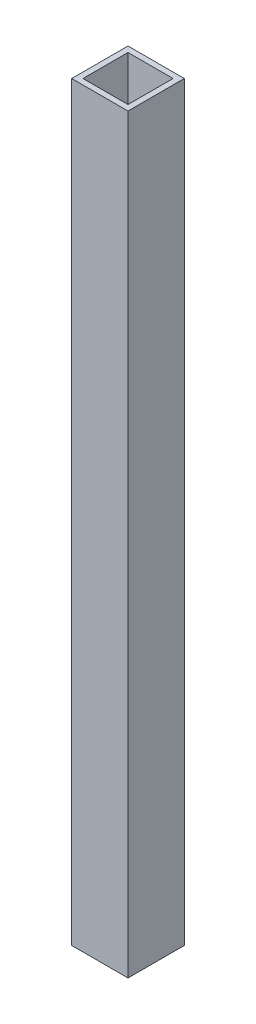
SolidWorks part; units mm, degrees
material "6061 Alloy"
ref_plane "Front Plane" through (0, 0, 0) normal (0, 0, 1) x (1, 0, 0)
ref_plane "Top Plane" through (0, 0, 0) normal (0, 1, 0) x (1, 0, 0)
ref_plane "Right Plane" through (0, 0, 0) normal (1, 0, 0) x (0, 0, -1)
sketch "Sketch1" plane through (0, 0, 0) normal (0, 1, 0) x (1, 0, 0)
  line L1 (0, 0) -> (15, 0)
  line L2 (0, 0) -> (0, 15)
  line L3 (0, 15) -> (15, 15)
  line L4 (15, 0) -> (15, 15)
  dimension "D1" = 15
extrude "Extrude-Thin1" add sketch "Sketch1" along normal blind 200 thin thin type one direction reverse wall 1.5
